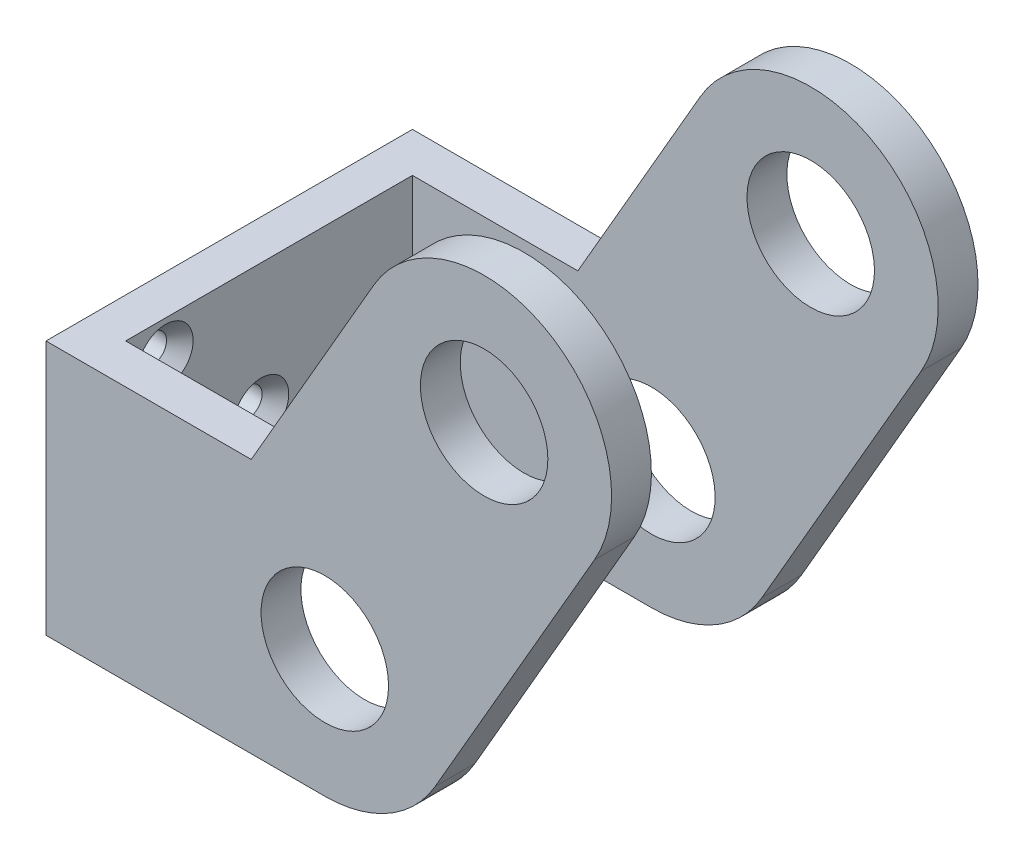
SolidWorks part; units mm, degrees
ref_plane "Front Plane" through (0, 0, 0) normal (0, 0, 1) x (1, 0, 0)
ref_plane "Top Plane" through (0, 0, 0) normal (0, 1, 0) x (1, 0, 0)
ref_plane "Right Plane" through (0, 0, 0) normal (1, 0, 0) x (0, 0, -1)
sketch "Sketch1" plane through (0, 0, 0) normal (0, 0, 1) x (1, 0, 0)
  line L0 (33.8564, 26.641) -> (13.8564, -8)
  line L1 (6.1436, 42.641) -> (-9.2376, 16)
  line L2 (0, -16) -> (-30, -16)
  line L3 (-30, -16) -> (-30, 16)
  line L4 (-30, 16) -> (-9.2376, 16)
  line L5 (33.8564, 26.641) -> (6.1436, 42.641) construction
  line L6 (0, 0) -> (20, 34.641) construction
  circle A0 centre (0, 0) radius 8
  circle A1 centre (20, 34.641) radius 8
  arc A2 (0, -16) -> (13.8564, -8) centre (0, 0) ccw
  arc A4 (6.1436, 42.641) -> (33.8564, 26.641) centre (20, 34.641) cw
  dimension "D1" = 120
  dimension "D2" = 16
  dimension "D3" = 32
  dimension "D4" = 30
  dimension "D5" = 40
extrude "Boss-Extrude1" add sketch "Sketch1" along normal blind 5 contours A4 L1 L4 L3 L2 A2 L0 A1 A0 region at (2.3653, 12.9987, 0)
sketch "Sketch2" plane through (-30, 0, 0) normal (-1, 0, 0) x (0, 0, 1)
  line L0 (5, -16) -> (0, -16) construction
  line L1 (5, 16) -> (-41, 16)
  line L2 (5, 16) -> (5, -16)
  line L3 (5, -16) -> (-41, -16)
  line L4 (-41, 16) -> (-41, -16)
  line L5 (5, 16) -> (0, 16) construction
  line L6 (5, -16) -> (5, 16) construction
  dimension "D1" = 46
extrude "Boss-Extrude2" add sketch "Sketch2" along normal blind 5
extrude "Boss-Extrude3" add sketch "Sketch1<2>" along normal blind 5 from surface contours A4 L1 L4 L3 L2 A2 L0 A1 A0 region at (2.3653, 12.9987, 0) starting at face at (-32.5, 0, -41)
sketch "Sketch1<2>" plane through (0, 0, 0) normal (0, 0, 1) x (1, 0, 0) same geometry as "Sketch1"
hole_wizard "CSK for M3 Hex Socket Countersunk Head Screw1" positions "Sketch5" profile "Sketch6" countersink size "M3" standard "DIN" end condition through all
sketch "Sketch5" plane through (-30, 0, 0) normal (1, 0, 0) x (0, 0, -1)
  circle A0 centre (17, 0) radius 2.1 construction
  circle A1 centre (5, 11.8262) radius 2.1 construction
  circle A2 centre (5, -11.8262) radius 2.1 construction
  circle A3 centre (17, 0) radius 2.1
  circle A4 centre (5, 11.8262) radius 2.1
  circle A5 centre (5, -11.8262) radius 2.1
  circle A6 centre (31, 0) radius 2.1 construction
  circle A7 centre (31, 0) radius 2.1
  point P1 (17, 0)
  point P3 (5, 11.8262)
  point P5 (5, -11.8262)
  point P10 (31, 0)
sketch "Sketch6" plane through (-30, 0, -17) normal (0, 1, 0) x (0, 0, -1)
  line L0 (0, 0) -> (0, 5)
  line L1 (0, 5) -> (1.8, 5)
  line L2 (1.8, 5) -> (1.8, 1.67)
  line L3 (1.8, 1.67) -> (3.47, 0)
  line L5 (3.47, 0) -> (0, 0)
  line L6 (-1.8, 1.67) -> (-3.47, 0) construction
  line L11 (0, -6.35) -> (0, 107.95) construction
  dimension "Thru Hole Dia." = 3.6
  dimension "Thru Hole Depth" = 5
  dimension "Near C'Sink Dia." = 6.94
  dimension "Near C'Sink Angle" = 90
